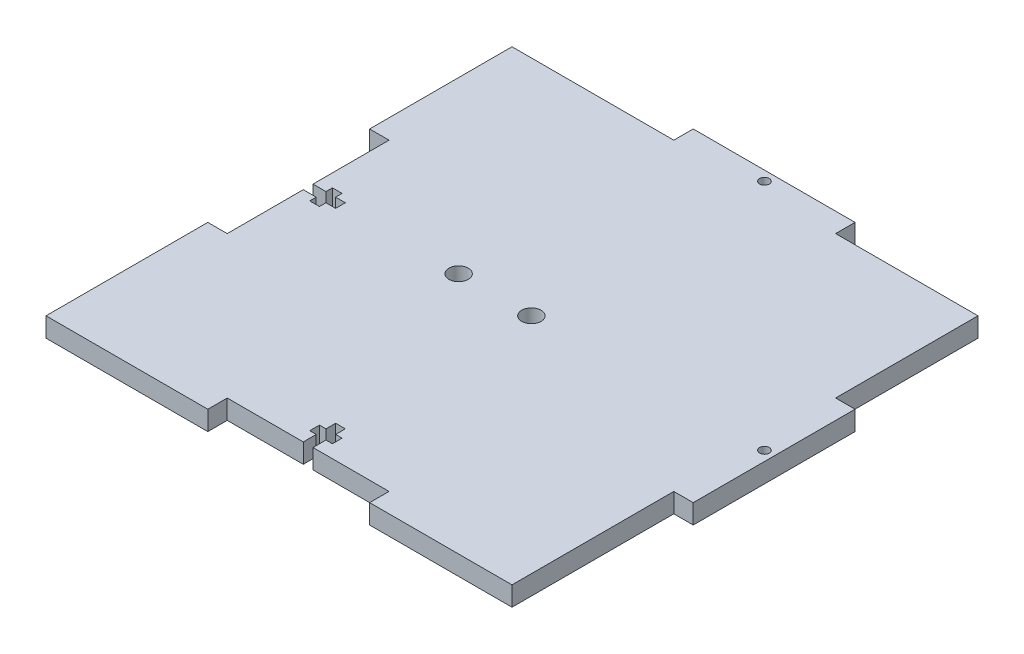
SolidWorks part; units mm, degrees
material "Acrylic (Medium-high impact)"
ref_plane "Front Plane" through (0, 0, 0) normal (0, 0, 1) x (1, 0, 0)
ref_plane "Top Plane" through (0, 0, 0) normal (0, 1, 0) x (1, 0, 0)
ref_plane "Right Plane" through (0, 0, 0) normal (1, 0, 0) x (0, 0, -1)
sketch "Sketch1" plane through (0, 0, 0) normal (0, 1, 0) x (1, 0, 0)
  line L0 (-72, 28) -> (-66, 28)
  line L1 (-72, -72) -> (72, -72)
  line L2 (-72, -72) -> (-72, 72)
  line L3 (-72, 72) -> (72, 72)
  line L4 (72, -72) -> (72, 72)
  line L5 (-72, -72) -> (72, 72) construction
  line L6 (-72, 72) -> (72, -72) construction
  line L7 (-66, 28) -> (-66, -22)
  line L8 (28, -72) -> (28, -66)
  line L9 (-22, 72) -> (-22, 78)
  line L10 (-22, 78) -> (28, 78)
  line L11 (28, 72) -> (28, 78)
  line L12 (72, 28) -> (78, 28)
  line L13 (78, 28) -> (78, -22)
  line L14 (-22, -72) -> (-22, -66)
  line L15 (-22, -66) -> (28, -66)
  line L16 (3, 78) -> (3, -72) construction
  line L17 (-72, 3) -> (78, 3) construction
  line L18 (72, -22) -> (78, -22)
  line L19 (-72, -22) -> (-66, -22)
  line L20 (75, 28) -> (75, -22) construction
  line L21 (4.5, -66) -> (4.5, -62)
  line L22 (4.5, -62) -> (6.5, -62)
  line L23 (6.5, -62) -> (6.5, -59)
  line L24 (6.5, -59) -> (4.5, -59)
  line L25 (4.5, -59) -> (4.5, -56)
  line L26 (4.5, -56) -> (1.5, -56)
  line L27 (1.5, -66) -> (1.5, -62)
  line L28 (1.5, -62) -> (-0.5, -62)
  line L29 (-0.5, -59) -> (1.5, -59)
  line L30 (-0.5, -62) -> (-0.5, -59)
  line L31 (1.5, -59) -> (1.5, -56)
  line L32 (-59, 4.5) -> (-56, 4.5)
  line L33 (-62, 4.5) -> (-62, 6.5)
  line L34 (-59, 6.5) -> (-59, 4.5)
  line L35 (-62, 6.5) -> (-59, 6.5)
  line L36 (-66, 4.5) -> (-62, 4.5)
  line L37 (-66, 1.5) -> (-62, 1.5)
  line L38 (-62, 1.5) -> (-62, -0.5)
  line L39 (-62, -0.5) -> (-59, -0.5)
  line L40 (-59, -0.5) -> (-59, 1.5)
  line L41 (-59, 1.5) -> (-56, 1.5)
  line L42 (-56, 4.5) -> (-56, 1.5)
  circle A0 centre (75, 3) radius 1.5
  circle A1 centre (3, 75) radius 1.5
  circle A2 centre (3, 3) radius 3
  circle A4 centre (-19.5, 3) radius 3
  point P0 (0, 0)
  point P22 (3, 3)
  point P27 (3, 3)
  point P40 (3, -66)
  point P45 (-66, 3)
  point P49 (3, -56)
  dimension "D4" = 3
  dimension "D9" = 6
  dimension "D1" = 144
  dimension "D2" = 25
  dimension "D3" = 6
  dimension "D5" = 4
  dimension "D6" = 2
  dimension "D7" = 3
  dimension "D8" = 1.5
  dimension "D10" = 2
extrude "Boss-Extrude1" add sketch "Sketch1" along normal blind 6 contours L19 L2 L1 L14 L15 L8 L4 L3 L0 L7 | L3 L11 L10 L9 | L4 L18 L13 L12 region at (-69.9635, 0, -50) region at (-21.4964, 0, -75) region at (75, 0, -27.4964)
